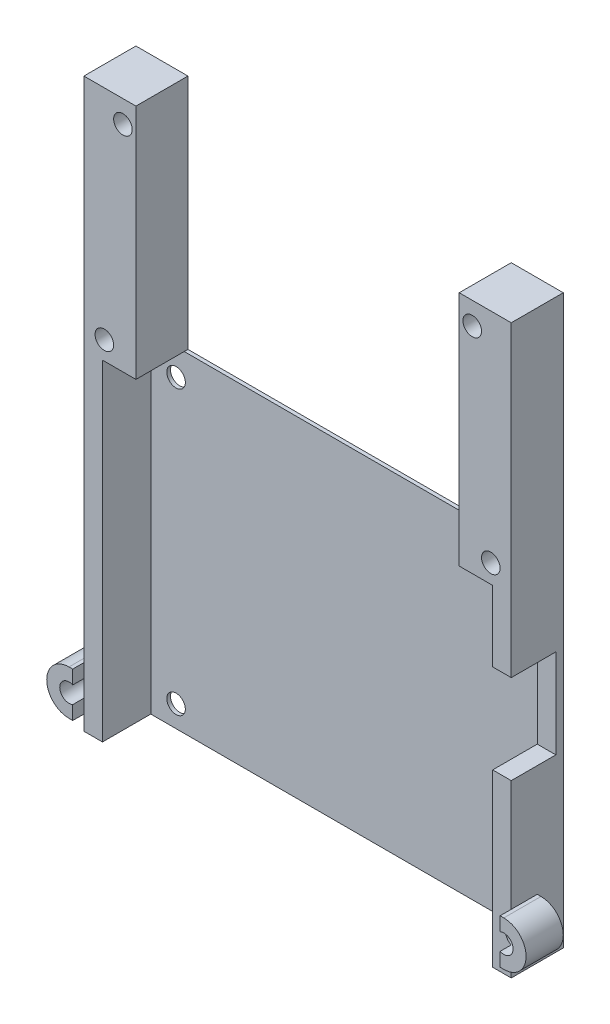
SolidWorks part; units mm, degrees
ref_plane "Front Plane" through (0, 0, 0) normal (0, 0, 1) x (1, 0, 0)
ref_plane "Top Plane" through (0, 0, 0) normal (0, 1, 0) x (1, 0, 0)
ref_plane "Right Plane" through (0, 0, 0) normal (1, 0, 0) x (0, 0, -1)
sketch "Sketch1" plane through (0, 0, 0) normal (0, 1, 0) x (1, 0, 0)
  line L0 (-28.75, 0) -> (-26.25, 0)
  line L1 (-28.75, 0) -> (28.75, 0) construction
  line L2 (-28.75, 0) -> (-28.75, 7)
  line L3 (-28.75, 7) -> (28.75, 7)
  line L4 (28.75, 0) -> (28.75, 7)
  line L5 (-26.25, 0) -> (-26.25, 6.5)
  line L6 (-26.25, 6.5) -> (26.25, 6.5)
  line L7 (26.25, 6.5) -> (26.25, 0)
  line L8 (26.25, 0) -> (28.75, 0)
  line L9 (0, 26.2156) -> (0, -12.2156) construction
  point P11 (0, 7)
  dimension "D1" = 57.5
  dimension "D2" = 7
  dimension "D4" = 6.5
  dimension "D3" = 2.5
  dimension "D5" = 52.5
extrude "Boss-Extrude1" add sketch "Sketch1" along normal blind 44.5
sketch "Sketch2" plane through (28.75, 0, 0) normal (1, 0, 0) x (0, 0, -1)
  line L0 (0, 0) -> (0, 23) construction
  line L1 (0, 44.5) -> (0, 0) construction
  line L2 (0, 23) -> (6, 23)
  line L3 (6, 23) -> (6, 35)
  line L4 (6, 35) -> (0, 35)
  line L5 (0, 35) -> (0, 23)
  dimension "D1" = 23
  dimension "D2" = 6
  dimension "D3" = 12
extrude "Cut-Extrude1" cut sketch "Sketch2" against normal blind 10
sketch "Sketch3" plane through (0, 0, -7) normal (0, 0, -1) x (-1, 0, 0)
  line L0 (-28.75, 0) -> (-28.75, 8) construction
  line L1 (-28.75, 44.5) -> (-28.75, 0) construction
  line L2 (-28.75, 8) -> (-28.75, 2)
  line L3 (-28.75, 5) -> (-29.25, 5) construction
  line L4 (-28.75, 8) -> (-29.25, 8)
  line L5 (-28.75, 2) -> (-29.25, 2)
  line L6 (28.75, 5) -> (29.25, 5) construction
  line L7 (0, 0) -> (0, 60.7094) construction
  line L11 (28.75, 0) -> (28.75, 8) construction
  line L12 (-28.75, 0) -> (28.75, 0) construction
  line L13 (28.75, 2) -> (29.25, 2)
  line L14 (28.75, 8) -> (29.25, 8)
  line L15 (28.75, 8) -> (28.75, 2)
  arc A0 (-29.25, 8) -> (-29.25, 2) centre (-29.25, 5) ccw
  circle A1 centre (-29.25, 5) radius 1.25
  circle A4 centre (29.25, 5) radius 1.25
  arc A5 (29.25, 8) -> (29.25, 2) centre (29.25, 5) cw
  line M5 (28.75, 0) -> (28.75, 44.5)
  line M7 (-28.75, 44.5) -> (-28.75, 0)
  dimension "D4" = 3
  dimension "D5" = 2.5
  dimension "D1" = 8
  dimension "D2" = 6
  dimension "D3" = 0.5
extrude "Boss-Extrude2" add sketch "Sketch3" against normal blind 8.5 contours A1 L4 A0 L5 M7 | L13 M5 region at (28.8195, 7.0728, -7) region at (-28.8195, 2.9272, -7)
extrude "Cut-Extrude2" cut sketch "Sketch3<3>" against normal blind 11 contours L2 A1 region at (28.4406, 5, -7)
sketch "Sketch3<3>" plane through (0, 0, -7) normal (0, 0, -1) x (-1, 0, 0) same geometry as "Sketch3"
sketch "Sketch4" plane through (0, 44.5, 0) normal (0, 1, 0) x (1, 0, 0)
  line L0 (28.75, 7) -> (-28.75, 7) construction
  line L1 (-28.75, 0) -> (-21.75, 0)
  line L2 (-28.75, 0) -> (-28.75, 7)
  line L3 (-28.75, 7) -> (-21.75, 7)
  line L4 (-21.75, 0) -> (-21.75, 7)
  line L5 (0, -3.8295) -> (0, 17.9405) construction
  line L6 (28.75, 0) -> (21.75, 0)
  line L7 (28.75, 0) -> (28.75, 7)
  line L8 (28.75, 7) -> (21.75, 7)
  line L9 (21.75, 0) -> (21.75, 7)
  dimension "D1" = 7
  dimension "D2" = 7
extrude "Boss-Extrude3" add sketch "Sketch4" along normal blind 5
sketch "Sketch9" plane through (0, 49.5, 0) normal (0, 1, 0) x (1, 0, 0)
  line L0 (0, -2.3135) -> (0, 15.8181) construction
  line L5 (21.75, 0) -> (28.75, 0)
  line L6 (21.75, 0) -> (21.75, 7)
  line L7 (21.75, 7) -> (28.75, 7)
  line L8 (28.75, 0) -> (28.75, 7)
  line L9 (-28.75, 0) -> (-28.75, 7)
  line L10 (-21.75, 7) -> (-28.75, 7)
  line L11 (-21.75, 0) -> (-21.75, 7)
  line L12 (-21.75, 0) -> (-28.75, 0)
extrude "Boss-Extrude5" add sketch "Sketch9" along normal blind 26.85
sketch "Sketch5" plane through (0, 0, -7) normal (0, 0, -1) x (-1, 0, 0)
  line L0 (-28.75, 0) -> (28.75, 0) construction
  line L2 (23.5, 73.35) -> (-23.5, 73.35) construction
  line L4 (-26, 47) -> (26, 47) construction
  line L6 (0, 73.35) -> (0, -5.4278) construction
  line L7 (-28.75, 76.35) -> (-21.75, 76.35) construction
  circle A0 centre (-26, 47) radius 1.25
  circle A1 centre (26, 47) radius 1.25
  circle A2 centre (-23.5, 73.35) radius 1.25
  circle A3 centre (23.5, 73.35) radius 1.25
  dimension "D1" = 2.5
  dimension "D2" = 47
  dimension "D3" = 26
  dimension "D5" = 3
  dimension "D6" = 47
extrude "Cut-Extrude3" cut sketch "Sketch5" against normal through all
sketch "Sketch7" plane through (0, 0, -7) normal (0, 0, -1) x (-1, 0, 0)
  line L0 (-28.75, 0) -> (-28.75, 2.9) construction
  line L1 (-28.75, 2) -> (-28.75, 0) construction
  line L2 (-28.75, 2.9) -> (28.75, 2.9) construction
  line L3 (28.75, 2) -> (28.75, 0) construction
  line L4 (-22.85, 2.9) -> (22.85, 2.9)
  line L5 (-22.85, 2.9) -> (-22.85, 40.95) construction
  line L7 (0, -3.4558) -> (0, 56.6048) construction
  circle A0 centre (-22.85, 2.9) radius 1.25
  circle A1 centre (22.85, 2.9) radius 1.25
  circle A2 centre (-22.85, 40.95) radius 1.25
  circle A3 centre (22.85, 40.95) radius 1.25
  point P11 (0, 2.9)
  dimension "D3" = 2.5
  dimension "D1" = 2.9
  dimension "D5" = 38.05
  dimension "D2" = 22.85
extrude "Cut-Extrude4" cut sketch "Sketch7" against normal blind 10 contours A2 | A3 | A1 | A0 region at (-22.85, 4.1146, -7) region at (24.0646, 2.9, -7) region at (22.85, 40.95, -7) region at (-22.85, 40.95, -7)
extrude "Cut-Extrude6" cut sketch "Sketch3<4>" against normal blind 3.5 contours A1 L4 A0 L5 M7 | L13 M5 region at (28.8195, 7.0728, -7) region at (-28.8195, 2.9272, -7)
sketch "Sketch3<4>" plane through (0, 0, -7) normal (0, 0, -1) x (-1, 0, 0) same geometry as "Sketch3"
extrude "Boss-Extrude4" add sketch "Sketch3<5>" against normal blind 3 contours L2 A1 region at (28.4406, 5, -7)
sketch "Sketch3<5>" plane through (0, 0, -7) normal (0, 0, -1) x (-1, 0, 0) same geometry as "Sketch3"
equation "\"D1@Sketch1\"=57.500000mm"
equation "\"D2@Sketch7\"=24.100000mm-1.25"
